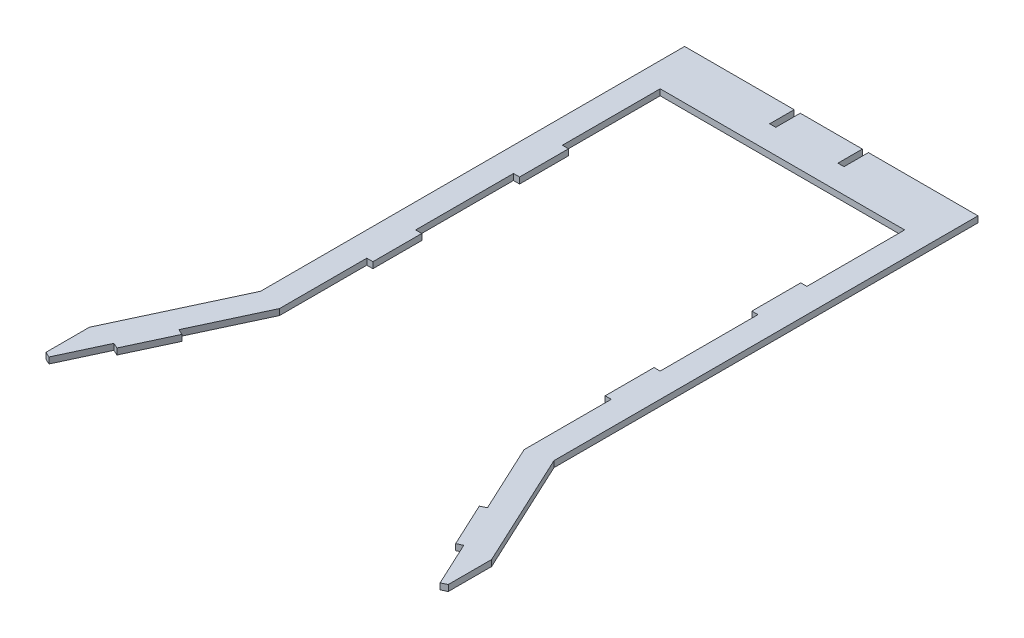
SolidWorks part; units mm, degrees
material "6061-T6 (SS)"
ref_plane "Front Plane" through (0, 0, 0) normal (0, 0, 1) x (1, 0, 0)
ref_plane "Top Plane" through (0, 0, 0) normal (0, 1, 0) x (1, 0, 0)
ref_plane "Right Plane" through (0, 0, 0) normal (1, 0, 0) x (0, 0, -1)
sketch "Sketch1" plane through (0, 0, 0) normal (0, 1, 0) x (1, 0, 0)
  line L0 (-76.2, 0) -> (76.2, 0)
  line L1 (-76.2, 0) -> (-76.2, -220.2788)
  line L3 (-63.5, -223.0943) -> (-63.5, -25.4)
  line L4 (-63.5, -25.4) -> (63.5, -25.4)
  line L5 (63.5, -25.4) -> (63.5, -223.0943)
  line L7 (76.2, -220.2788) -> (76.2, 0)
  line L8 (-76.2, -220.2788) -> (-113.1101, -299.4327)
  line L9 (-113.1101, -299.4327) -> (-101.6, -304.8)
  line L10 (-101.6, -304.8) -> (-63.5, -223.0943)
  line L11 (63.5, -223.0943) -> (101.6, -304.8)
  line L12 (76.2, -220.2788) -> (113.1101, -299.4327)
  line L13 (113.1101, -299.4327) -> (101.6, -304.8)
  point P4 (0, 0)
  dimension "D1" = 127
  dimension "D3" = 25.4
  dimension "D5" = 12.7
  dimension "D6" = 12.7
  dimension "D8" = 12.7
  dimension "D9" = 38.1
  dimension "D10" = 279.4
  dimension "D12" = 25
base flange "Base-Flange1" sketch "Sketch1" thickness 3.175 reverse thickness direction no parameters "D1"=3.175
sketch "Sketch7" plane through (0, 0, 0) normal (0, 1, 0) x (1, 0, 0)
  line L0 (-19.304, 0) -> (-19.304, -12.7)
  line L1 (76.2, 0) -> (-76.2, 0) construction
  line L2 (-19.304, -12.7) -> (-16.129, -12.7)
  line L3 (-16.129, -12.7) -> (-16.129, 0)
  line L4 (-16.129, 0) -> (-19.304, 0)
  line L9 (0, 0) -> (0, -25.4) construction
  line L10 (-63.5, -25.4) -> (63.5, -25.4) construction
  line L11 (16.129, 0) -> (19.304, 0)
  line L14 (16.129, -12.7) -> (16.129, 0)
  line L16 (19.304, -12.7) -> (16.129, -12.7)
  line L17 (19.304, 0) -> (19.304, -12.7)
  dimension "D1" = 12.7
  dimension "D2" = 3.175
  dimension "D3" = 32.258
extrude "Cut-Extrude1" cut sketch "Sketch7" against normal through all normal cut yes
sketch "Sketch12" plane through (0, 0, 0) normal (0, 1, 0) x (1, 0, 0)
  line L0 (-63.5, -223.0943) -> (-63.5, -25.4) construction
  line L1 (-63.5, -76.2) -> (-60.325, -76.2)
  line L2 (-63.5, -76.2) -> (-63.5, -101.6)
  line L3 (-63.5, -101.6) -> (-60.325, -101.6)
  line L4 (-60.325, -76.2) -> (-60.325, -101.6)
  line L5 (-80.131, -258.7596) -> (-90.8655, -281.7798)
  line L6 (-63.5, -152.4) -> (-60.325, -152.4)
  line L7 (-63.5, -152.4) -> (-63.5, -177.8)
  line L8 (-63.5, -177.8) -> (-60.325, -177.8)
  line L9 (-60.325, -152.4) -> (-60.325, -177.8)
  line L10 (-80.131, -258.7596) -> (-77.2535, -260.1014)
  line L11 (-90.8655, -281.7798) -> (-87.988, -283.1216)
  line L12 (-77.2535, -260.1014) -> (-87.988, -283.1216)
  line L13 (-101.6, -304.8) -> (-63.5, -223.0943) construction
  line L18 (-113.1101, -299.4327) -> (-101.6, -304.8) construction
  line L19 (0, 0) -> (0, -305.8108) construction
  line L24 (-63.5, -25.4) -> (63.5, -25.4) construction
  line L25 (77.2535, -260.1014) -> (87.988, -283.1216)
  line L26 (90.8655, -281.7798) -> (87.988, -283.1216)
  line L27 (80.131, -258.7596) -> (77.2535, -260.1014)
  line L28 (60.325, -152.4) -> (60.325, -177.8)
  line L29 (63.5, -177.8) -> (60.325, -177.8)
  line L30 (63.5, -152.4) -> (63.5, -177.8)
  line L31 (63.5, -152.4) -> (60.325, -152.4)
  line L32 (80.131, -258.7596) -> (90.8655, -281.7798)
  line L33 (60.325, -76.2) -> (60.325, -101.6)
  line L34 (63.5, -101.6) -> (60.325, -101.6)
  line L35 (63.5, -76.2) -> (63.5, -101.6)
  line L36 (63.5, -76.2) -> (60.325, -76.2)
  dimension "D1" = 25.4
  dimension "D2" = 3.175
  dimension "D3" = 50.8
  dimension "D4" = 50.8
  dimension "D5" = 25.4
base flange "Tab1" sketch "Sketch12" thickness 3.175 reverse thickness direction no parameters "D1"=3.175
sketch "Sketch13" plane through (0, 0, 0) normal (0, 1, 0) x (1, 0, 0)
  line L0 (-104.4775, -303.4582) -> (-104.4775, -280.9201)
  line L1 (-113.1101, -299.4327) -> (-101.6, -304.8) construction
  line L2 (-76.2, -220.2788) -> (-113.1101, -299.4327) construction
  line L3 (104.4775, -303.4582) -> (104.4775, -280.9201)
  line L4 (101.6, -304.8) -> (113.1101, -299.4327) construction
  line L5 (113.1101, -299.4327) -> (76.2, -220.2788) construction
  line L6 (-104.4775, -280.9201) -> (-113.1101, -299.4327)
  line L7 (-113.1101, -299.4327) -> (-104.4775, -303.4582)
  line L8 (104.4775, -303.4582) -> (113.1101, -299.4327)
  line L9 (113.1101, -299.4327) -> (104.4775, -280.9201)
  line L10 (-101.6, -304.8) -> (-90.8655, -281.7798) construction
  dimension "D1" = 3.175
extrude "Cut-Extrude2" cut sketch "Sketch13" against normal through all normal cut yes
sketch "Bend-Lines1" [suppressed] plane through (0, 0, 0) normal (0, 1, 0) x (1, 0, 0)
sketch "Bounding-Box1" [suppressed] plane through (0, 0, 0) normal (0, 1, 0) x (1, 0, 0)
sheet metal parameters "Sheet-Metal1" thickness 3.175 parameters "D1"=3.175
flat pattern "Flat-Pattern1" [suppressed]
sketch "Bend-Lines2" plane through (0, 0, 0) normal (0, 1, 0) x (1, 0, 0)
sketch3d "Bounding-Box2" [suppressed]
  line L0 (-150.221, -355.6, 0) -> (-150.221, 0, 0) construction
  line L1 (150.221, -355.6, 0) -> (150.221, 0, 0) construction
  line L2 (-150.221, -355.6, 0) -> (150.221, -355.6, 0) construction
  line L3 (-150.221, 0, 0) -> (150.221, 0, 0) construction
sheet metal parameters "Sheet-Metal2" thickness 3.175 parameters "D1"=3.175
flat pattern "Flat-Pattern1"
sketch "Bend-Lines2" plane through (0, 0, 0) normal (0, 1, 0) x (1, 0, 0)
sketch3d "Bounding-Box2" [suppressed]
  line L0 (-125.2985, -304.8, 0) -> (-125.2985, 0, 0) construction
  line L1 (125.2985, -304.8, 0) -> (125.2985, 0, 0) construction
  line L2 (-125.2985, -304.8, 0) -> (125.2985, -304.8, 0) construction
  line L3 (-125.2985, 0, 0) -> (125.2985, 0, 0) construction
sheet metal parameters "Sheet-Metal3" thickness 3.175 parameters "D1"=3.175
flat pattern "Flat-Pattern3"
sketch "Bend-Lines3" plane through (0, 0, 0) normal (0, 1, 0) x (1, 0, 0)
sketch3d "Bounding-Box3" [suppressed]
  line L0 (126.0258, -302.871, 0) -> (73.6666, 15.3992, 0) construction
  line L1 (28.3517, -318.9395, 0) -> (-24.0075, -0.6693, 0) construction
  line L2 (126.0258, -302.871, 0) -> (28.3517, -318.9395, 0) construction
  line L3 (73.6666, 15.3992, 0) -> (-24.0075, -0.6693, 0) construction
sheet metal parameters "Sheet-Metal4" thickness 3.175 parameters "D1"=3.175
flat pattern "Flat-Pattern4"
sketch "Bend-Lines4" plane through (0, 0, 0) normal (0, 1, 0) x (1, 0, 0)
sketch3d "Bounding-Box4" [suppressed]
  line L0 (-126.0258, -302.871, 0) -> (-74.8011, 8.5031, 0) construction
  line L1 (-70.2702, -312.0434, 0) -> (-19.0455, -0.6693, 0) construction
  line L2 (-126.0258, -302.871, 0) -> (-70.2702, -312.0434, 0) construction
  line L3 (-74.8011, 8.5031, 0) -> (-19.0455, -0.6693, 0) construction
sheet metal parameters "Sheet-Metal5" thickness 3.175 parameters "D1"=3.175
flat pattern "Flat-Pattern5"
sketch "Bend-Lines5" plane through (0, 0, 0) normal (0, 1, 0) x (1, 0, 0)
sketch3d "Bounding-Box5" [suppressed]
  line L0 (-113.1101, -304.8, 0) -> (-113.1101, 0, 0) construction
  line L1 (113.1101, -304.8, 0) -> (113.1101, 0, 0) construction
  line L2 (-113.1101, -304.8, 0) -> (113.1101, -304.8, 0) construction
  line L3 (-113.1101, 0, 0) -> (113.1101, 0, 0) construction
sheet metal parameters "Sheet-Metal6" thickness 3.175 parameters "D1"=3.175
flat pattern "Flat-Pattern5"
sketch "Bend-Lines5" plane through (0, 0, 0) normal (0, 1, 0) x (1, 0, 0)
sketch3d "Bounding-Box5" [suppressed]
  line L0 (-104.4775, -304.8, 0) -> (-104.4775, 0, 0) construction
  line L1 (104.4775, -304.8, 0) -> (104.4775, 0, 0) construction
  line L2 (-104.4775, -304.8, 0) -> (104.4775, -304.8, 0) construction
  line L3 (-104.4775, 0, 0) -> (104.4775, 0, 0) construction
